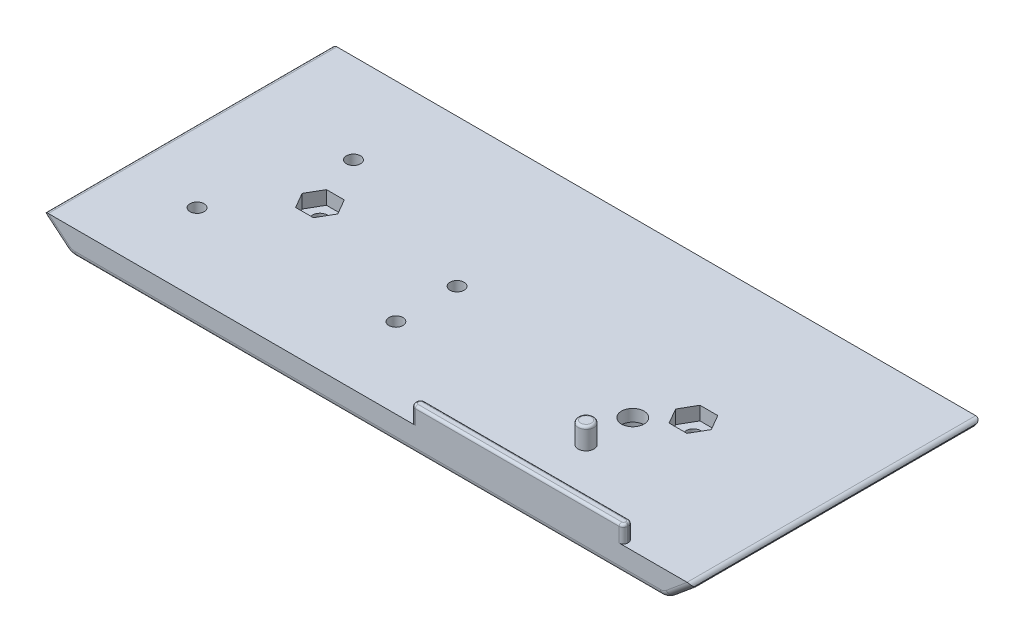
SolidWorks part; units mm, degrees
other "Markup1"
sketch "Sketch8" plane through (63.5, 12.7, 43.18) normal (0.1457, 0.8684, 0.474) x (0.9558, 0, -0.2939)
ref_plane "Front Plane" through (0, 0, 0) normal (0, 0, 1) x (1, 0, 0)
ref_plane "Top Plane" through (0, 0, 0) normal (0, 1, 0) x (1, 0, 0)
ref_plane "Right Plane" through (0, 0, 0) normal (1, 0, 0) x (0, 0, -1)
sketch "Sketch1" plane through (0, 0, 0) normal (0, 1, 0) x (1, 0, 0)
  line L1 (98.425, -43.18) -> (-98.425, -43.18)
  line L2 (98.425, -43.18) -> (98.425, 43.18)
  line L3 (98.425, 43.18) -> (-98.425, 43.18)
  line L4 (-98.425, -43.18) -> (-98.425, 43.18)
  line L5 (0, 43.18) -> (0, -43.18) construction
  line L6 (98.425, 0) -> (-98.425, 0) construction
  point P0 (0, 0)
  dimension "D1" = 86.36
  dimension "D2" = 196.85
extrude "Boss-Extrude1" add sketch "Sketch1" along normal blind 7.62
sketch "Sketch6" plane through (0, 7.62, 0) normal (0, 1, 0) x (1, 0, 0)
  line L0 (-98.425, -43.18) -> (98.425, -43.18) construction
  circle A0 centre (46.355, -22.606) radius 2.3495
  dimension "D1" = 4.699
  dimension "D2" = 20.574
  dimension "D3" = 46.355
sketch "Sketch7" plane through (0, 7.62, 0) normal (0, 1, 0) x (1, 0, 0)
  line L1 (14.605, -43.18) -> (78.105, -43.18)
  line L2 (14.605, -43.18) -> (14.605, -40.386)
  line L3 (14.605, -40.386) -> (78.105, -40.386)
  line L4 (78.105, -43.18) -> (78.105, -40.386)
  point P4 (46.355, -43.18)
  dimension "D1" = 63.5
  dimension "D2" = 2.794
  dimension "D3" = 46.355
extrude "Boss-Extrude3" add sketch "Sketch7" along normal blind 5.08
fillet "Fillet1" radius 1.27 4 edges at (14.605, 10.16, 40.386) (14.605, 10.16, 43.18) (78.105, 10.16, 40.386) (78.105, 10.16, 43.18)
extrude "Boss-Extrude4" add sketch "Sketch6" along normal blind 6.35
sketch "Sketch11" plane through (0, 7.62, 0) normal (0, 1, 0) x (1, 0, 0)
  line L0 (-98.425, -43.18) -> (15.875, -43.18) construction
  circle A0 centre (-48.26, 10.16) radius 3.3782
  dimension "D1" = 6.7564
  dimension "D2" = 48.26
  dimension "D3" = 53.34
sketch "Sketch13" plane through (0, 7.62, 0) normal (0, 1, 0) x (1, 0, 0)
  line L0 (0, -43.18) -> (0, 43.18) construction
  line L1 (-98.425, -43.18) -> (15.875, -43.18) construction
  line L2 (98.425, 43.18) -> (-98.425, 43.18) construction
sketch "Sketch14" plane through (0, 7.62, 0) normal (0, 1, 0) x (1, 0, 0)
  line L0 (98.425, 43.18) -> (-98.425, 43.18) construction
  line L1 (-53.213, 4.6194) -> (-58.547, 4.6194)
  line L2 (-58.547, 4.6194) -> (-61.214, 0)
  line L3 (-61.214, 0) -> (-58.547, -4.6194)
  line L4 (-58.547, -4.6194) -> (-53.213, -4.6194)
  line L5 (-53.213, -4.6194) -> (-50.546, 0)
  line L6 (-50.546, 0) -> (-53.213, 4.6194)
  line L7 (61.214, 0) -> (58.547, 4.6194)
  line L8 (58.547, 4.6194) -> (53.213, 4.6194)
  line L9 (53.213, 4.6194) -> (50.546, 0)
  line L10 (50.546, 0) -> (53.213, -4.6194)
  line L11 (53.213, -4.6194) -> (58.547, -4.6194)
  line L12 (58.547, -4.6194) -> (61.214, 0)
  circle A0 centre (-55.88, 0) radius 4.6194 construction
  circle A1 centre (55.88, 0) radius 4.6194 construction
  dimension "D1" = 55.88
  dimension "D2" = 55.88
  dimension "D3" = 10.668
  dimension "D4" = 10.668
extrude "Cut-Extrude3" cut sketch "Sketch14" against normal blind 4.064
sketch "Sketch15" plane through (0, 3.556, 0) normal (0, 1, 0) x (1, 0, 0)
  circle A0 centre (-55.88, 0) radius 2.2479
  circle A1 centre (55.88, 0) radius 2.2479
  dimension "D1" = 4.4958
  dimension "D2" = 4.4958
extrude "Cut-Extrude4" cut sketch "Sketch15" against normal through all
sketch "Sketch17" plane through (0, 7.62, 0) normal (0, 1, 0) x (1, 0, 0)
  circle A0 centre (46.355, -8.636) radius 3.3782
  dimension "D1" = 6.7564
  dimension "D2" = 13.97
extrude "Cut-Extrude5" cut sketch "Sketch17" against normal through all
sketch "Sketch18" plane through (0, 7.62, 0) normal (0, 1, 0) x (1, 0, 0)
  line L1 (-4.445, -43.18) -> (97.155, -43.18)
  line L2 (-4.445, -43.18) -> (-4.445, 53.34)
  line L3 (-4.445, 53.34) -> (97.155, 53.34)
  line L4 (97.155, -43.18) -> (97.155, 53.34)
  line L7 (-7.62, -26.035) -> (-83.82, -26.035)
  line L8 (-7.62, -26.035) -> (-7.62, 46.355)
  line L9 (-7.62, 46.355) -> (-83.82, 46.355)
  line L10 (-83.82, -26.035) -> (-83.82, 46.355)
  dimension "D1" = 50.8
  dimension "D2" = 50.8
  dimension "D3" = 40.64
  dimension "D4" = 35.56
  dimension "D5" = 36.195
  dimension "D6" = 72.39
  dimension "D7" = 96.52
sketch "Sketch19" plane through (0, 0, 0) normal (0, -1, 0) x (1, 0, 0)
  circle A0 centre (46.355, 8.636) radius 6.858
  dimension "D1" = 13.716
extrude "Cut-Extrude6" cut sketch "Sketch19" against normal blind 4.064
sketch "Sketch20" plane through (-98.425, 0, 0) normal (-1, 0, 0) x (0, 0, 1)
  line L1 (-48.1675, 20.2108) -> (71.5087, 20.2108)
  line L2 (-48.1675, 20.2108) -> (-48.1675, -11.455)
  line L3 (-48.1675, -11.455) -> (71.5087, -11.455)
  line L4 (71.5087, 20.2108) -> (71.5087, -11.455)
extrude "Cut-Extrude7" cut sketch "Sketch20" against normal blind 3.175
sketch "Sketch21" plane through (0, 7.62, 0) normal (0, 1, 0) x (1, 0, 0)
  line L0 (-13.97, -19.177) -> (-13.97, -0.889)
  line L1 (98.425, -43.18) -> (-98.425, -43.18) construction
  line L2 (-73.2282, 16.3833) -> (-62.23, 16.3833)
  line L3 (-73.2282, -19.431) -> (-73.2282, 16.3833)
  line L4 (-62.23, 16.3833) -> (-73.2282, -19.431)
  circle A1 centre (-55.88, 0) radius 2.2479 construction
  dimension "D3" = 41.91
  dimension "D1" = 18.288
  dimension "D2" = 24.003
  dimension "D4" = 37.465
  dimension "D5" = 23.749
  dimension "D6" = 10.9982
  dimension "D7" = 6.35
hole_wizard "M3 Clearance Hole1" positions "Sketch24" profile "Sketch25" hole size "M3" standard "ANSI Metric" end condition through all
sketch "Sketch24" plane through (0, 0, 0) normal (0, -1, 0) x (-1, 0, 0)
  point P0 (13.97, -19.177)
  point P3 (13.97, -0.889)
  point P6 (73.2282, -19.431)
  point P9 (62.23, 16.3833)
sketch "Sketch25" plane through (-13.97, 0, 19.177) normal (1, 0, 0) x (0, 0, -1)
  line L0 (0, 0) -> (0, 13.97)
  line L1 (0, 13.97) -> (2.1, 13.97)
  line L2 (2.1, 13.97) -> (2.1, 0)
  line L5 (2.1, 0) -> (0, 0)
  line L11 (0, -6.35) -> (0, 107.95) construction
  dimension "Thru Hole Dia." = 4.2
  dimension "Thru Hole Depth" = 13.97
sketch "Sketch26" plane through (0, 0, 0) normal (0, -1, 0) x (1, 0, 0)
  circle A0 centre (-73.2282, 19.431) radius 3.05
  circle A1 centre (-62.23, -16.3833) radius 3.05
  circle A2 centre (-13.97, 0.889) radius 3.05
  circle A3 centre (-13.97, 19.177) radius 3.05
  dimension "D1" = 6.1
extrude "Cut-Extrude8" cut sketch "Sketch26" against normal blind 4
chamfer "Chamfer1" distance 7.62 distance2 6.35 2 edges at (98.425, 0, 0) (-95.25, 0, 0) first distance on face at (-73.2282, 0, 16.381)
fillet "Fillet5" radius 1.27 4 edges at (-95.25, 7.62, 0) (-95.25, 6.35, 0) (98.425, 6.35, 0) (98.425, 7.62, 0)
fillet "Fillet6" radius 4.318 2 edges at (90.805, 0, 0) (-87.63, 0, 0)
fillet "Fillet7" radius 1.778 10 edges at (-91.812, 3.485, 43.18) (-87.5366, 0.2579, 43.18) (94.987, 3.485, 43.18) (90.7116, 0.2579, 43.18) (1.5875, 0, 43.18) (90.7116, 0.2579, -43.18) (94.987, 3.485, -43.18) (-91.812, 3.485, -43.18) (-87.5366, 0.2579, -43.18) (1.5875, 0, -43.18)
fillet "Fillet8" radius 0.762 9 edges at (14.977, 12.7, 42.808) (14.605, 12.7, 41.783) (14.977, 12.7, 40.758) (46.355, 12.7, 40.386) (77.733, 12.7, 40.758) (78.105, 12.7, 41.783) (77.733, 12.7, 42.808) (46.355, 12.7, 43.18) (46.355, 13.97, 24.9555)
